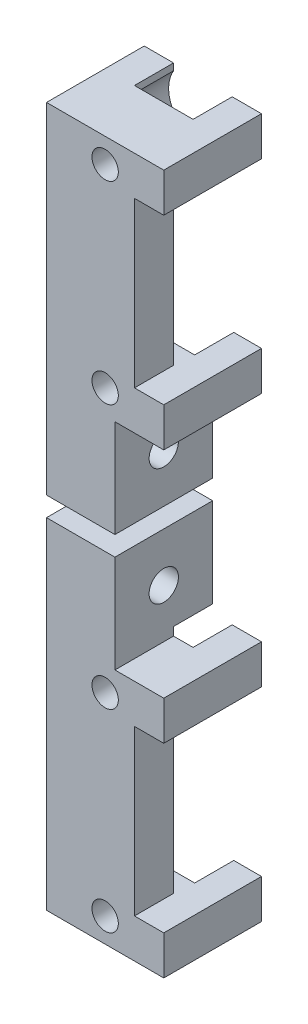
SolidWorks part; units mm, degrees
ref_plane "Front Plane" through (0, 0, 0) normal (0, 0, 1) x (1, 0, 0)
ref_plane "Top Plane" through (0, 0, 0) normal (0, 1, 0) x (1, 0, 0)
ref_plane "Right Plane" through (0, 0, 0) normal (1, 0, 0) x (0, 0, -1)
ref_axis "Axis2" through (0, 11, 0) along (0, -1, 0)
ref_plane "Plane2" through (0, 0, -150) normal (0, 0, 1) x (1, 0, 0)
sketch "Sketch7" plane through (0, 0, -150) normal (0, 0, 1) x (1, 0, 0)
  line L1 (-6, 24.8) -> (6, 24.8)
  line L2 (-6, 24.8) -> (-6, 0)
  line L4 (6, 24.8) -> (6, 0)
  line L7 (-6, 0) -> (6, 0)
  point P6 (6, 0)
  point P8 (0, 0)
  point P11 (0, 24.8)
  dimension "D1" = 24.8
  dimension "D2" = 12
extrude "Main" add sketch "Sketch7" along normal mid plane 10
sketch "Sketch8" plane through (0, 0, -145) normal (0, 0, 1) x (1, 0, 0)
  line L1 (-6, 24.8) -> (-6, 0) construction
  line L2 (6, 24.8) -> (-6, 24.8) construction
  circle A0 centre (0, 22.3) radius 1.35
  circle A1 centre (0, 2.5) radius 1.35
  dimension "D1" = 2.7
  dimension "D2" = 2.5
  dimension "D3" = 19.8
  dimension "D4" = 6
extrude "Holes" cut sketch "Sketch8" against normal through all
sketch "Sketch16" plane through (6, 0, 0) normal (1, 0, 0) x (0, 0, -1)
  line L1 (149, 20.8) -> (155, 20.8)
  line L2 (149, 20.8) -> (149, 4)
  line L3 (149, 4) -> (155, 4)
  line L4 (155, 20.8) -> (155, 4)
  line L5 (155, 0) -> (155, 24.8) construction
  dimension "D1" = 6
  dimension "D2" = 4
  dimension "D3" = 4
extrude "FixExtrusion" cut sketch "Sketch16" against normal through all
sketch "Sketch17" plane through (0, 0, -155) normal (0, 0, -1) x (-1, 0, 0)
  line L0 (-6, 24.8) -> (6, 24.8) construction
  line L1 (-3, 24.8) -> (3, 24.8)
  line L2 (-3, 24.8) -> (-3, 0)
  line L3 (-3, 0) -> (3, 0)
  line L4 (3, 24.8) -> (3, 0)
  line L5 (6, 0) -> (-6, 0) construction
  line L6 (-6, 20.8) -> (-6, 24.8) construction
  dimension "D1" = 6
  dimension "D2" = 3
extrude "Cut-Extrude1" cut sketch "Sketch17" against normal blind 4
sketch "Sketch18" plane through (0, 0, -149) normal (0, 0, -1) x (-1, 0, 0)
  line L0 (6, 4) -> (-6, 4) construction
  line L1 (-6, 20.8) -> (-3, 20.8)
  line L2 (-6, 20.8) -> (-6, 4)
  line L3 (-6, 4) -> (-3, 4)
  line L4 (-3, 20.8) -> (-3, 4)
  dimension "D1" = 3
extrude "Cut-Extrude2" cut sketch "Sketch18" against normal through all
sketch "Sketch19" plane through (0, 0, 0) normal (0, -1, 0) x (1, 0, 0)
  line L0 (1, -155) -> (-6, -155)
  line L1 (-6, -155) -> (-6, -151.45)
  line L2 (-6, -151.45) -> (-7, -151.45)
  line L3 (-7, -151.45) -> (-7, -148.55)
  line L4 (-7, -148.55) -> (-6, -148.55)
  line L5 (-6, -148.55) -> (-6, -145)
  line L6 (-6, -145) -> (1, -145)
  line L7 (1, -145) -> (1, -155)
  line L8 (6, -145) -> (-6, -145) construction
  line L9 (-6, -145) -> (-6, -155) construction
  dimension "D1" = 10
  dimension "D2" = 1
  dimension "D3" = 2.9
  dimension "D4" = 7
extrude "Boss-Extrude1" add sketch "Sketch19" along normal blind 10
sketch "Sketch20" plane through (1, 0, 0) normal (1, 0, 0) x (0, 0, -1)
  line L0 (155, -10) -> (145, -10) construction
  line L1 (155, -10) -> (155, 0) construction
  circle A0 centre (150, -5) radius 1.5
  point P4 (150, -10)
  dimension "D1" = 3
  dimension "D2" = 5
  dimension "D3" = 5
extrude "Cut-Extrude3" cut sketch "Sketch20" against normal through all
sketch "Sketch21" plane through (0, 0, -155) normal (0, 0, -1) x (-1, 0, 0)
  circle A0 centre (0, 2.5) radius 3.5
  circle A1 centre (0, 2.5) radius 1.35 construction
  circle A2 centre (0, 22.3) radius 3.5
  circle A3 centre (0, 22.3) radius 1.35 construction
  dimension "D1" = 7
extrude "Cut-Extrude4" cut sketch "Sketch21" against normal up to surface (4 mm away) up to face at (0.2, 1.6, -151)
ref_plane "Plane3" through (0, -11, 0) normal (0, -1, 0) x (-1, 0, 0)
mirror "Mirror2" about plane through (0, -11, 0) normal (0, -1, 0) of bodies 145
